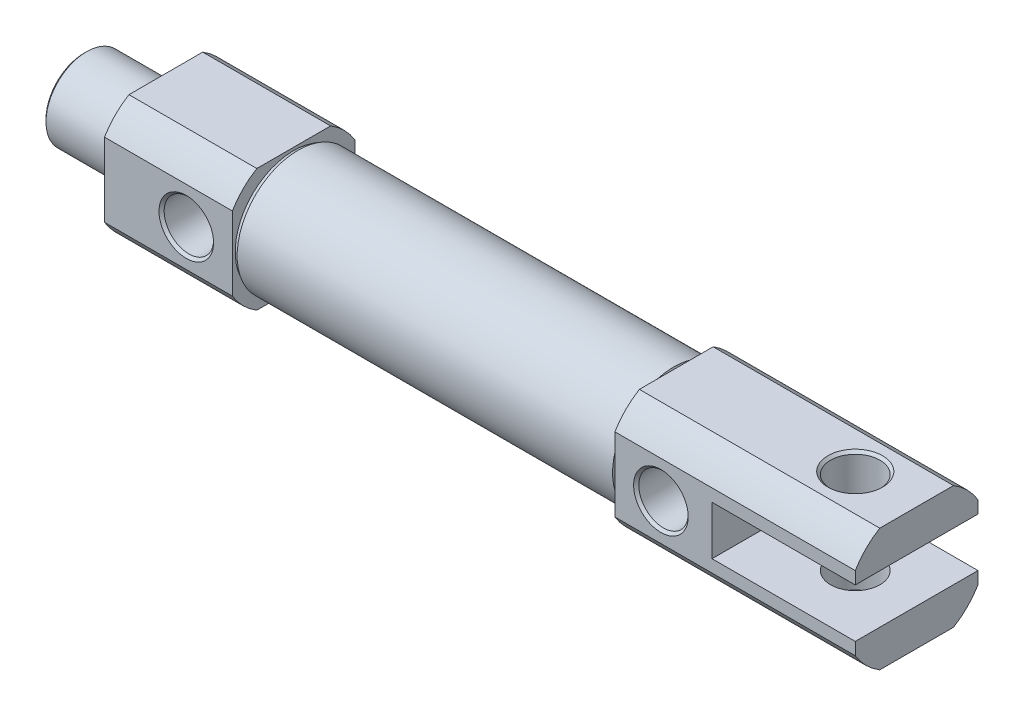
SolidWorks part; units mm, degrees
ref_plane "Front Plane" through (0, 0, 0) normal (0, 0, 1) x (1, 0, 0)
ref_plane "Top Plane" through (0, 0, 0) normal (0, 1, 0) x (1, 0, 0)
ref_plane "Right Plane" through (0, 0, 0) normal (1, 0, 0) x (0, 0, -1)
sketch "Sketch1" plane through (0, 0, 0) normal (1, 0, 0) x (0, 0, -1)
  circle A0 centre (0, 0) radius 5
  circle A1 centre (0, 0) radius 5.97
  dimension "D1" = 10
  dimension "D2" = 11.94
extrude "Boss-Extrude1" add sketch "Sketch1" along normal mid plane 30.4 contours A0 region at (0, 0, 0)
extrude "Boss-Extrude2" add sketch "Sketch1<3>" along normal mid plane 37.4
sketch "Sketch1<3>" plane through (0, 0, 0) normal (1, 0, 0) x (0, 0, -1) same geometry as "Sketch1"
chamfer "Chamfer1" distance 0.254 angle 60 1 edges at (18.7, 0, -5.97) first distance on face at (18.7, 0, -5.97)
chamfer "Chamfer2" distance 0.254 angle 60 1 edges at (-18.7, 0, -5.97) first distance on face at (-18.7, 0, -5.97)
sketch "Sketch2" plane through (18.7, 0, 0) normal (1, 0, 0) x (0, 0, -1)
  line L1 (6, -6) -> (-6, -6)
  line L2 (6, -6) -> (6, 6)
  line L3 (6, 6) -> (-6, 6)
  line L4 (-6, -6) -> (-6, 6)
  line L5 (6, -6) -> (-6, 6) construction
  line L6 (6, 6) -> (-6, -6) construction
  circle A0 centre (0, 0) radius 7
  point P0 (0, 0)
  dimension "D3" = 14
  dimension "D1" = 12
  dimension "D2" = 12
sketch "Sketch3" plane through (18.7, 0, 0) normal (1, 0, 0) x (0, 0, -1)
  line L0 (-6, 3.6055) -> (-6, -3.6055)
  line L1 (6, 3.6055) -> (6, -3.6055)
  line L2 (-3.6055, 6) -> (3.6055, 6)
  line L3 (-3.6055, -6) -> (3.6055, -6)
  line L4 (6, -6) -> (6, 6) construction
  line L5 (6, 6) -> (-6, 6) construction
  line L6 (-6, -6) -> (-6, 6) construction
  line L7 (6, -6) -> (-6, -6) construction
  arc A0 (-6, 3.6055) -> (-3.6055, 6) centre (0, 0) cw
  arc A1 (6, 3.6055) -> (3.6055, 6) centre (0, 0) ccw
  arc A2 (6, -3.6055) -> (3.6055, -6) centre (0, 0) cw
  arc A3 (-6, -3.6055) -> (-3.6055, -6) centre (0, 0) ccw
  circle A4 centre (0, 0) radius 7 construction
extrude "Boss-Extrude3" add sketch "Sketch3" along normal blind 23.5001
sketch "Sketch5" plane through (0, 6, 0) normal (0, 1, 0) x (1, 0, 0)
  line L0 (42.2001, 3.6055) -> (42.2001, -3.6055) construction
  circle A0 centre (36.2001, 0) radius 2.415
  dimension "D2" = 4.8301
  dimension "D1" = 6
extrude "Cut-Extrude2" cut sketch "Sketch5" against normal through all
sketch "Sketch6" plane through (0, 0, 6) normal (0, 0, 1) x (1, 0, 0)
  line L0 (42.2001, 3.6055) -> (42.2001, -3.6055) construction
  line L1 (28.2001, -2.39) -> (42.2001, -2.39)
  line L2 (28.2001, -2.39) -> (28.2001, 2.39)
  line L3 (28.2001, 2.39) -> (42.2001, 2.39)
  line L4 (42.2001, -2.39) -> (42.2001, 2.39)
  line L5 (28.2001, -2.39) -> (42.2001, 2.39) construction
  line L6 (28.2001, 2.39) -> (42.2001, -2.39) construction
  point P0 (35.2001, 0)
  dimension "D1" = 14
  dimension "D2" = 4.78
extrude "Cut-Extrude3" cut sketch "Sketch6" against normal through all
extrude "Boss-Extrude4" add sketch "Sketch3<2>" against normal blind 12.5001 from surface starting at face at (-18.7, 0, -5.716)
sketch "Sketch3<2>" plane through (18.7, 0, 0) normal (1, 0, 0) x (0, 0, -1) same geometry as "Sketch3"
sketch "Sketch4" plane through (0, 0, 6) normal (0, 0, 1) x (1, 0, 0)
  line L0 (18.7, 3.6055) -> (18.7, -3.6055) construction
  line L1 (-18.7, 3.6055) -> (-18.7, -3.6055) construction
  circle A0 centre (23.2001, 0) radius 2.415
  circle A1 centre (-23.2001, 0) radius 2.415
  dimension "D2" = 4.8301
  dimension "D1" = 4.5001
  dimension "D3" = 4.5001
extrude "Cut-Extrude4" cut sketch "Sketch4" against normal blind 6
sketch "Sketch8" plane through (-31.2001, 0, 0) normal (-1, 0, 0) x (0, 0, 1)
  circle A0 centre (0, 0) radius 3.9688
  circle A1 centre (0, 0) radius 2.1827
  dimension "D1" = 4.3655
  dimension "D2" = 7.9375
extrude "Boss-Extrude5" add sketch "Sketch8" along normal blind 8
chamfer "Chamfer5" distance 0.254 angle 45 6 edges at (36.2001, -6, 2.415) (36.2001, 6, 2.415) (25.6151, 0, 6) (-20.7851, 0, 6) (-39.2001, 0, 3.9688) (-39.2001, 0, 2.1827)
equation "\"D2@Sketch2\"=\"D1@Sketch2\""
